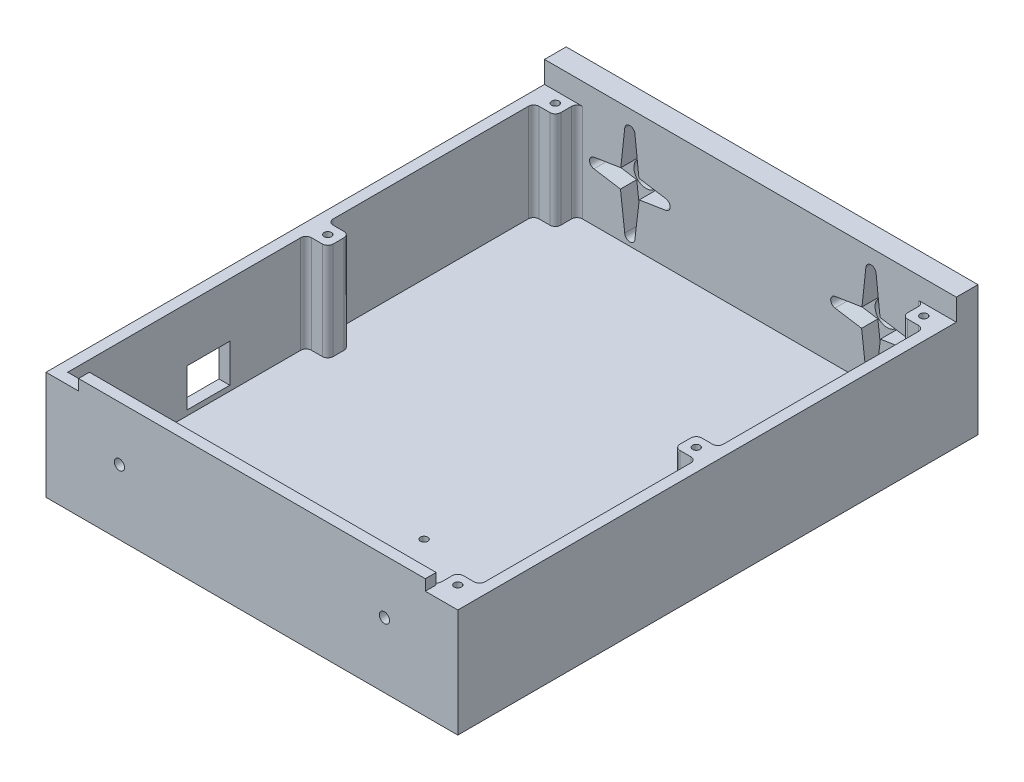
SolidWorks part; units mm, degrees
material "ABS"
ref_plane "Front" through (0, 0, 0) normal (0, 0, 1) x (1, 0, 0)
ref_plane "Top" through (0, 0, 0) normal (0, 1, 0) x (1, 0, 0)
ref_plane "Right" through (0, 0, 0) normal (1, 0, 0) x (0, 0, -1)
sketch "Sketch1" plane through (0, 0, 0) normal (0, 1, 0) x (1, 0, 0)
  line L1 (-60.325, 76.2) -> (60.325, 76.2)
  line L2 (-60.325, 76.2) -> (-60.325, -76.2)
  line L3 (-60.325, -76.2) -> (60.325, -76.2)
  line L4 (60.325, 76.2) -> (60.325, -76.2)
  line L5 (-60.325, 76.2) -> (60.325, -76.2) construction
  line L6 (-60.325, -76.2) -> (60.325, 76.2) construction
  line L11 (-57.15, 69.85) -> (57.15, 69.85)
  line L12 (-57.15, 69.85) -> (-57.15, -73.025)
  line L13 (-57.15, -73.025) -> (57.15, -73.025)
  line L14 (57.15, 69.85) -> (57.15, -73.025)
  point P0 (0, 0)
  point P6 (0, 0)
  dimension "D1" = 3.175
  dimension "D2" = 152.4
  dimension "D3" = 114.3
  dimension "D4" = 3.175
  dimension "D5" = 3.175
  dimension "D6" = 6.35
extrude "Boss-Extrude1" add sketch "Sketch1" along normal blind 3.175 contours L4 L3 L2 L1
extrude "Boss-Extrude2" add sketch "Sketch1<3>" along normal blind 38.1
sketch "Sketch1<3>" plane through (0, 0, 0) normal (0, 1, 0) x (1, 0, 0) same geometry as "Sketch1"
sketch "Sketch2" plane through (0, 0, 76.2) normal (0, 0, 1) x (1, 0, 0)
  line L0 (38.825, 19.05) -> (60.325, 19.05) construction
  line L1 (60.325, 38.1) -> (60.325, 0) construction
  circle A0 centre (38.825, 19.05) radius 1.5
  dimension "D2" = 3
  dimension "D1" = 21.5
extrude "Cut-Extrude1" cut sketch "Sketch2" against normal up to surface (3.175 mm away) up to face at (0, 20.6375, 73.025)
sketch "Sketch3" plane through (0, 0, -69.85) normal (0, 0, 1) x (1, 0, 0)
  line L0 (60.325, 19.05) -> (35.325, 19.05) construction
  line L1 (60.325, 38.1) -> (60.325, 0) construction
  line L2 (36.825, 5.8) -> (38.138, 16.8438)
  line L3 (33.825, 5.8) -> (32.5119, 16.8438)
  line L4 (32.6352, 21.4049) -> (33.8337, 32.4617)
  line L5 (38.0148, 21.4049) -> (36.8163, 32.4617)
  line L6 (24.7882, 17.5688) -> (33.1188, 16.2369)
  line L7 (24.7882, 20.5312) -> (33.1188, 21.863)
  line L9 (33.1188, 21.863) -> (33.1188, 16.2369) construction
  line L10 (37.5312, 21.863) -> (45.8618, 20.5312)
  line L11 (37.5312, 16.237) -> (45.8618, 17.5688)
  arc A0 (32.6352, 21.4049) -> (32.5119, 16.8438) centre (35.325, 19.05) ccw
  arc A1 (33.825, 5.8) -> (36.825, 5.8) centre (35.325, 5.8) ccw
  arc A2 (32.6352, 21.4049) -> (32.5119, 16.8438) centre (35.325, 19.05) ccw construction
  arc A10 (33.8337, 32.4617) -> (36.8163, 32.4617) centre (35.325, 32.3) cw
  arc A11 (38.138, 16.8438) -> (38.0148, 21.4049) centre (35.325, 19.05) ccw
  arc A12 (38.138, 16.8438) -> (38.0148, 21.4049) centre (35.325, 19.05) ccw construction
  arc A13 (24.7882, 20.5312) -> (24.7882, 17.5688) centre (25.025, 19.05) ccw
  arc A14 (37.5312, 21.863) -> (37.5312, 16.237) centre (35.325, 19.05) cw
  arc A15 (33.1188, 16.2369) -> (33.1188, 21.863) centre (35.325, 19.05) cw
  arc A16 (45.8618, 20.5312) -> (45.8618, 17.5688) centre (45.625, 19.05) cw
  circle A17 centre (35.325, 19.05) radius 3.575
  dimension "D1" = 7.15
  dimension "D3" = 3
  dimension "D6" = 14.75
  dimension "D7" = 3
  dimension "D2" = 25
  dimension "D4" = 14.75
  dimension "D5" = 5.6261
  dimension "D8" = 5.6261
  dimension "D9" = 11.8
extrude "Cut-Extrude8" cut sketch "Sketch3" against normal blind 4.7625 contours A16 L10 L5 A11 L2 L11 | A17 L10 L5 A10 L4 L7 | A17 L6 L3 A1 L2 L11 | L4 A15 L7 | L2 A14 L11 | L6 A15 L3 | L6 A15 L7 A13 | A14 L11 A16 L10 region at (35.325, 10.8168, -69.85) region at (37.9239, 16.4606, -69.85) region at (42.2416, 19.0536, -69.85) region at (32.7261, 16.4606, -69.85) region at (35.325, 27.3342, -69.85) region at (32.8048, 21.6911, -69.85)
extrude "Cut-Extrude9" cut sketch "Sketch3<8>" against normal through all contours A14 A17 A15 A0 A11 region at (35.325, 19.05, -69.85)
sketch "Sketch3<8>" plane through (0, 0, -69.85) normal (0, 0, 1) x (1, 0, 0) same geometry as "Sketch3"
mirror "Mirror1" about plane through (0, 0, 0) normal (1, 0, 0) of "Cut-Extrude9", "Cut-Extrude1", "Cut-Extrude8"
sketch "Sketch4" plane through (-57.15, 0, 0) normal (1, 0, 0) x (0, 0, -1)
  line L0 (-73.025, 15.876) -> (-38.025, 15.876) construction
  line L1 (-73.025, 38.1) -> (-73.025, 3.175) construction
  line L3 (-38.025, 15.876) -> (-25.525, 15.876)
  line L4 (-38.025, 15.876) -> (-38.025, 4.7)
  line L5 (-38.025, 4.7) -> (-25.525, 4.7)
  line L6 (-25.525, 15.876) -> (-25.525, 4.7)
  line L7 (76.2, 0) -> (-76.2, 0) construction
  dimension "D1" = 35
  dimension "D2" = 11.176
  dimension "D3" = 12.5
  dimension "D4" = 4.7
extrude "Cut-Extrude10" cut sketch "Sketch4" against normal up to next
sketch "Sketch5" plane through (0, 3.175, 0) normal (0, 1, 0) x (1, 0, 0)
  line L0 (-57.15, -34.596) -> (8.85, -34.596) construction
  line L1 (-57.15, 69.85) -> (-57.15, -73.025) construction
  line L2 (-60.325, -38.025) -> (-57.15, -38.025) construction
  line L3 (8.85, -34.596) -> (8.85, -62.6122) construction
  point P7 (8.85, -34.596)
  point P9 (8.85, -62.6122)
  dimension "D1" = 3.429
  dimension "D2" = 66
  dimension "D3" = 28.0162
hole_wizard "#2 Clearance Hole1" positions "3DSketch1" profile "Sketch7" hole size "#2" standard "ANSI Inch" end condition up to next
sketch3d "3DSketch1"
  point P0 (8.85, 3.175, 62.6122)
  point P3 (8.85, 3.175, 34.596)
sketch "Sketch7" plane through (8.85, 3.175, 62.6122) normal (1, 0, 0) x (0, 0, 1)
  line L0 (0, 0) -> (0, 3.175)
  line L1 (0, 3.175) -> (1.0795, 3.175)
  line L2 (1.0795, 3.175) -> (1.0795, 0)
  line L5 (1.0795, 0) -> (0, 0)
  line L11 (0, -6.35) -> (0, 107.95) construction
  dimension "Thru Hole Dia." = 2.159
  dimension "Thru Hole Depth" = 3.175
sketch "Sketch8" plane through (0, 38.1, 0) normal (0, 1, 0) x (1, 0, 0)
  line L1 (-60.325, -76.2) -> (-50.8, -76.2)
  line L2 (-60.325, -76.2) -> (-60.325, 69.85)
  line L3 (-60.325, 69.85) -> (-50.8, 69.85)
  line L4 (-50.8, -76.2) -> (-50.8, 69.85)
  line L5 (60.325, -76.2) -> (50.8, -76.2)
  line L6 (60.325, -76.2) -> (60.325, 69.85)
  line L7 (60.325, 69.85) -> (50.8, 69.85)
  line L8 (50.8, -76.2) -> (50.8, 69.85)
  line L9 (-60.325, 69.85) -> (60.325, 69.85)
  line L10 (-60.325, 69.85) -> (-60.325, -76.2)
  line L11 (-60.325, -76.2) -> (60.325, -76.2)
  line L12 (60.325, 69.85) -> (60.325, -76.2)
  line M8 (60.325, -76.2) -> (60.325, 76.2)
  line M10 (-60.325, 76.2) -> (-60.325, -76.2)
  line M11 (-60.325, -76.2) -> (60.325, -76.2)
  line M12 (57.15, -73.025) -> (-57.15, -73.025)
  line M13 (-57.15, -73.025) -> (-57.15, 69.85)
  line M15 (57.15, 69.85) -> (57.15, -73.025)
  dimension "D1" = 9.525
  dimension "D2" = 146.05
extrude "Cut-Extrude11" cut sketch "Sketch8" against normal blind 3.175 contours L9 L4 L8 M12 | L4 L3 M12 M13 | L4 L3 M11 M12 M13 M10 | L8 L7 M12 M15 | L8 L7 M11 M8 M15 M12 | L10 L9 L12 L11 region at (-58.5391, 38.1, 6.1516) region at (-53.975, 38.1, 1.5875) region at (0, 38.1, 1.5875) region at (58.5391, 38.1, 6.1516) region at (53.975, 38.1, 1.5875)
extrude "Cut-Extrude13" cut sketch "Sketch8<6>" against normal blind 6.35 contours L4 L3 M11 M12 M13 M10 | L4 L3 M12 M13 | L8 L7 M12 M15 | L8 L7 M11 M8 M15 M12 region at (-58.5391, 38.1, 6.1516) region at (-53.975, 38.1, 1.5875) region at (58.5391, 38.1, 6.1516) region at (53.975, 38.1, 1.5875)
sketch "Sketch8<6>" plane through (0, 38.1, 0) normal (0, 1, 0) x (1, 0, 0) same geometry as "Sketch8"
sketch "Sketch9" plane through (0, 3.175, 0) normal (0, 1, 0) x (1, 0, 0)
  line L0 (-57.15, 69.85) -> (-57.15, -73.025) construction
  line L1 (-50.8, -3.175) -> (-57.15, -3.175)
  line L2 (-50.8, -3.175) -> (-50.8, 3.175)
  line L3 (-50.8, 3.175) -> (-57.15, 3.175)
  line L4 (-57.15, -3.175) -> (-57.15, 3.175)
  line L5 (-50.8, -3.175) -> (-57.15, 3.175) construction
  line L6 (-50.8, 3.175) -> (-57.15, -3.175) construction
  line L7 (57.15, -73.025) -> (57.15, 69.85) construction
  line L8 (50.8, 3.175) -> (57.15, 3.175)
  line L9 (50.8, 3.175) -> (50.8, -3.175)
  line L10 (50.8, -3.175) -> (57.15, -3.175)
  line L11 (57.15, 3.175) -> (57.15, -3.175)
  line L12 (50.8, 3.175) -> (57.15, -3.175) construction
  line L13 (50.8, -3.175) -> (57.15, 3.175) construction
  line L15 (57.15, -73.025) -> (50.8, -73.025)
  line L16 (57.15, -73.025) -> (57.15, -66.675)
  line L17 (57.15, -66.675) -> (50.8, -66.675)
  line L18 (50.8, -73.025) -> (50.8, -66.675)
  line L19 (-57.15, 69.85) -> (-50.8, 69.85)
  line L20 (-57.15, 69.85) -> (-57.15, 63.5)
  line L21 (-57.15, 63.5) -> (-50.8, 63.5)
  line L22 (-50.8, 69.85) -> (-50.8, 63.5)
  line L23 (57.15, 69.85) -> (50.8, 69.85)
  line L24 (57.15, 69.85) -> (57.15, 63.5)
  line L25 (57.15, 63.5) -> (50.8, 63.5)
  line L26 (50.8, 69.85) -> (50.8, 63.5)
  point P0 (-53.975, 0)
  point P9 (53.975, 0)
  dimension "D1" = 6.35
extrude "Boss-Extrude3" add sketch "Sketch9" along normal up to surface (28.575 mm away) up to face at (-56.0917, 31.75, 26.4583)
fillet "Fillet1" radius 1.5875 17 edges at (57.15, 17.4625, 66.675) (50.8, 17.4625, 66.675) (50.8, 17.4625, 73.025) (57.15, 17.4625, -3.175) (50.8, 17.4625, -3.175) (50.8, 17.4625, 3.175) (57.15, 17.4625, 3.175) (-57.15, 17.4625, -3.175) (-50.8, 17.4625, -3.175) (-50.8, 17.4625, 3.175) (-57.15, 17.4625, 3.175) (57.15, 17.4625, -63.5) (50.8, 17.4625, -63.5) (50.8, 17.4625, -69.85) (-57.15, 17.4625, -63.5) (-50.8, 17.4625, -63.5) (-50.8, 17.4625, -69.85)
hole_wizard "#2 Clearance Hole2" positions "Sketch10" profile "Sketch12" hole size "#2" standard "ANSI Inch"
sketch "Sketch10" plane through (0, 31.75, 0) normal (0, 1, 0) x (1, 0, 0)
  line L0 (-53.975, 3.175) -> (-53.975, -3.175) construction
  line L1 (-52.3875, 3.175) -> (-55.5625, 3.175) construction
  line L2 (-55.5625, -3.175) -> (-52.3875, -3.175) construction
  line L4 (53.975, 3.175) -> (53.975, -3.175) construction
  line L5 (55.5625, 3.175) -> (52.3875, 3.175) construction
  line L6 (52.3875, -3.175) -> (55.5625, -3.175) construction
  line L8 (53.975, -66.675) -> (53.975, -69.85) construction
  line L9 (55.5625, -66.675) -> (52.3875, -66.675) construction
  line L10 (53.975, -69.85) -> (50.8, -69.85) construction
  line L11 (50.8, -68.2625) -> (50.8, -71.4375) construction
  line L12 (-53.975, 63.5) -> (-53.975, 66.675) construction
  line L13 (-55.5625, 63.5) -> (-52.3875, 63.5) construction
  line L14 (-53.975, 66.675) -> (-50.8, 66.675) construction
  line L15 (-50.8, 65.0875) -> (-50.8, 68.2625) construction
  line L17 (50.8, 66.675) -> (53.975, 66.675) construction
  line L18 (50.8, 68.2625) -> (50.8, 65.0875) construction
  line L19 (53.975, 66.675) -> (53.975, 63.5) construction
  line L20 (52.3875, 63.5) -> (55.5625, 63.5) construction
  point P19 (53.975, -69.85)
  point P30 (53.975, 0)
  point P32 (-53.975, 0)
  point P35 (-53.975, 66.675)
  point P44 (53.975, 66.675)
sketch "Sketch12" plane through (53.975, 31.75, -66.675) normal (1, 0, 0) x (0, 0, 1)
  line L0 (0, 0) -> (0, 13.3486)
  line L1 (0, 13.3486) -> (1.0795, 12.7)
  line L2 (1.0795, 12.7) -> (1.0795, 0)
  line L5 (1.0795, 0) -> (0, 0)
  line L10 (0, 13.3486) -> (-1.0795, 12.7) construction
  line L11 (0, -6.35) -> (0, 107.95) construction
  dimension "Hole Dia." = 2.159
  dimension "Hole Depth" = 12.7
  dimension "Drill Angle" = 118
